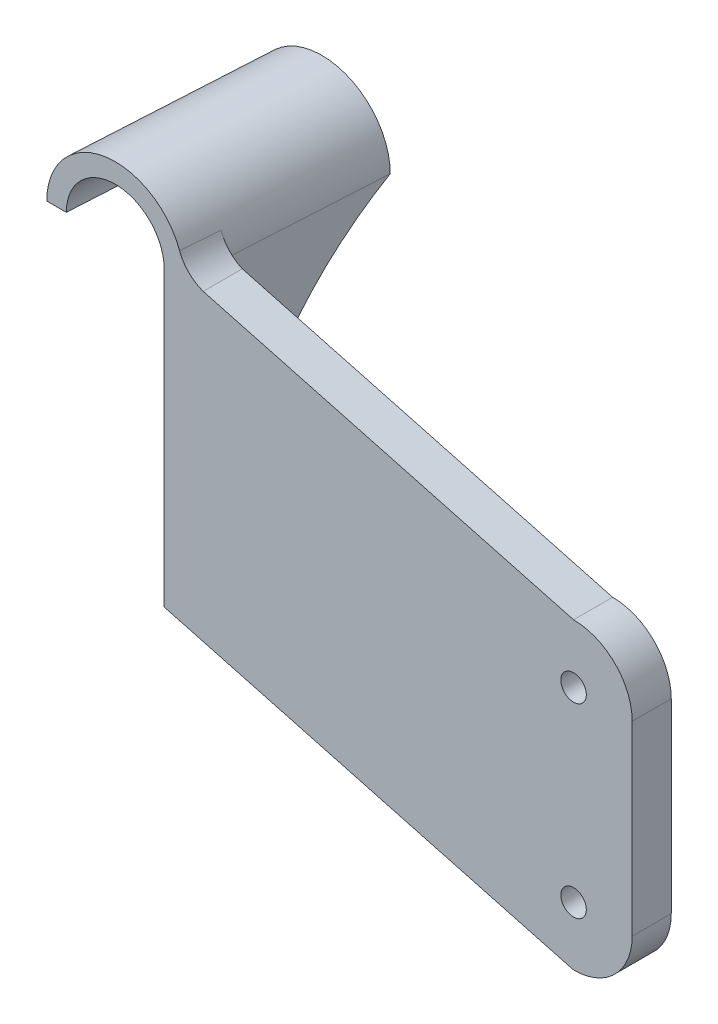
SolidWorks part; units mm, degrees
ref_plane "Front Plane" through (0, 0, 0) normal (0, 0, 1) x (1, 0, 0)
ref_plane "Top Plane" through (0, 0, 0) normal (0, 1, 0) x (1, 0, 0)
ref_plane "Right Plane" through (0, 0, 0) normal (1, 0, 0) x (0, 0, -1)
sketch "Sketch1" plane through (0, 0, 0) normal (0, 0, 1) x (1, 0, 0)
  line L0 (0, -23.8125) -> (0, 23.8125)
  line L1 (-15, -38.8125) -> (-120, -38.8125)
  line L2 (-15, -38.8125) -> (-119.7785, -10.7372)
  line L3 (-15, 38.8125) -> (-119.7785, 66.8878)
  line L4 (-119.7785, -10.7372) -> (-119.7785, 66.8878)
  arc A0 (0, 23.8125) -> (-15, 38.8125) centre (-15, 23.8125) ccw
  circle A1 centre (-15, 23.8125) radius 3.2639
  circle A2 centre (-15, -23.8125) radius 3.2639
  arc A3 (0, -23.8125) -> (-15, -38.8125) centre (-15, -23.8125) cw
  point P8 (-111.1285, 58.222)
  dimension "D2" = 30
  dimension "D3" = 6.5278
  dimension "D7" = 6.5278
  dimension "D1" = 47.625
  dimension "D4" = 105
  dimension "D5" = 15
  dimension "D6" = 108.4747
extrude "Boss-Extrude1" add sketch "Sketch1" along normal blind 10 contours A3 L0 A0 L3 L4 L2 A1 A2
sketch "Sketch2" plane through (0, 0, 10) normal (0, 0, 1) x (1, 0, 0)
  line L0 (-109.7785, 64.2083) -> (-109.7785, 103.7647)
  line L1 (-15, 38.8125) -> (-119.7785, 66.8878) construction
  line L2 (-109.7785, 103.7647) -> (-165.743, 103.7647)
  line L3 (-165.743, 103.7647) -> (-165.743, 64.2083)
  line L4 (-165.743, 64.2083) -> (-109.7785, 64.2083)
  dimension "D1" = 10
extrude "Boss-Extrude2" add sketch "Sketch2" against normal blind 50
ref_plane "Plane1" through (-0.9592, 0, 16.7887) normal (-0.057, 0, 0.9984) x (0, 1, 0)
sketch "Sketch4" plane through (-0.9592, 0, 16.7887) normal (-0.057, 0, 0.9984) x (0, 1, 0)
  line L1 (64.2083, 144.013) -> (64.2083, 119.013)
  line L3 (64.2083, 149.013) -> (64.2083, 176.7001)
  line L4 (64.2083, 164.9027) -> (64.2083, 119.013) construction
  line L5 (64.2083, 176.7001) -> (111.9846, 176.7001)
  line L6 (111.9846, 176.7001) -> (111.9846, 106.9013)
  line L7 (111.9846, 106.9013) -> (64.2083, 106.9013)
  line L8 (64.2083, 106.9013) -> (64.2083, 114.013)
  arc A0 (64.2083, 119.013) -> (64.2083, 144.013) centre (64.2083, 131.513) ccw
  arc A1 (64.2083, 114.013) -> (64.2083, 149.013) centre (64.2083, 131.513) ccw
  dimension "D1" = 25
  dimension "D3" = 35
extrude "Cut-Extrude1" cut sketch "Sketch4" against normal through all and the other way through all contours A1 L8 L7 L6 L5 L3 | L1 A0
fillet "Fillet1" radius 10 1 edges at (-114.4846, 64.2083, 5)
sketch "Sketch7" plane through (0, 64.2083, 0) normal (0, 1, 0) x (1, 0, 0)
  line L0 (-119.7785, 0) -> (-119.2071, 0)
  line L1 (-119.2071, 0) -> (-119.7785, -10)
  line L2 (-119.7785, -10) -> (-119.7785, 0)
  point P4 (-119.7785, -0.0106)
extrude "Cut-Extrude3" cut sketch "Sketch7" against normal through all
sketch "Sketch8" plane through (0, 64.2083, 0) normal (0, -1, 0) x (1, 0, 0)
  line L0 (-119.2071, 0) -> (-116.9218, -40)
  line L1 (-116.9218, -40) -> (-111.9136, -40)
  line L2 (-111.9136, -40) -> (-114.199, 0)
  line L3 (-114.199, 0) -> (-119.2071, 0)
extrude "Boss-Extrude3" add sketch "Sketch8" along normal up to surface (77.0529 mm away)
sketch "Sketch10" plane through (-113.8274, 0, -6.5035) normal (0.9984, 0, 0.057) x (0.057, 0, -0.9984)
  circle A0 centre (83.4725, -10.6773) radius 90
extrude "Cut-Extrude4" cut sketch "Sketch10" against normal blind 50
fillet "Fillet4" [suppressed] radius 5
